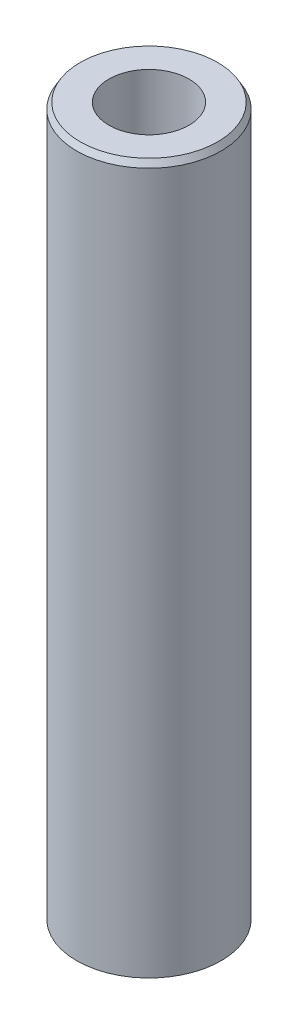
SolidWorks part; units mm, degrees
ref_plane "Front Plane" through (0, 0, 0) normal (0, 0, 1) x (1, 0, 0)
ref_plane "Top Plane" through (0, 0, 0) normal (0, 1, 0) x (1, 0, 0)
ref_plane "Right Plane" through (0, 0, 0) normal (1, 0, 0) x (0, 0, -1)
sketch "Sketch1" plane through (0, 0, 0) normal (0, 1, 0) x (1, 0, 0)
  circle A0 centre (0, 0) radius 15
  dimension "SHAFT_OD" = 30
extrude "Boss-Extrude1" add sketch "Sketch1" along normal blind 147.4784
sketch "Sketch2" plane through (0, 0, 0) normal (0, 1, 0) x (1, 0, 0)
  circle A0 centre (0, 0) radius 8.3113
  dimension "BORE_D" = 16.6226
extrude "Cut-Extrude1" cut sketch "Sketch2" along normal through all
chamfer "Chamfer1" distance 1.2755 angle 30 2 edges at (0, 147.4784, 15) (0, 0, 15) first distance on face at (0, 147.4784, 15) first distance on face at (0, 0, 8.3113)
